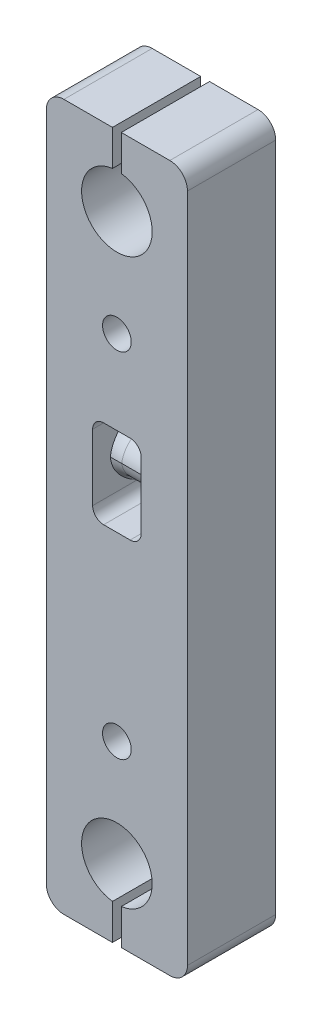
SolidWorks part; units mm, degrees
ref_plane "Front Plane" through (0, 0, 0) normal (0, 0, 1) x (1, 0, 0)
ref_plane "Top Plane" through (0, 0, 0) normal (0, 1, 0) x (1, 0, 0)
ref_plane "Right Plane" through (0, 0, 0) normal (1, 0, 0) x (0, 0, -1)
sketch "Sketch1" plane through (0, 0, 0) normal (0, 0, 1) x (1, 0, 0)
  line L0 (8, 72) -> (8, 8) construction
  line L1 (0, 0) -> (16, 0)
  line L2 (0, 0) -> (0, 80)
  line L3 (0, 80) -> (16, 80)
  line L4 (16, 0) -> (16, 80)
  line L5 (8, 8) -> (8, 0) construction
  line L6 (6.5, 49.25) -> (9.5, 49.25) construction
  line L7 (6.5, 50.5) -> (9.5, 50.5)
  line L8 (6.5, 48) -> (9.5, 48)
  line L9 (6.5, 41.75) -> (9.5, 41.75) construction
  line L10 (6.5, 43) -> (9.5, 43)
  line L11 (6.5, 40.5) -> (9.5, 40.5)
  line L12 (8, 40) -> (16, 40) construction
  circle A0 centre (8, 72) radius 4
  circle A1 centre (8, 8) radius 4
  arc A2 (6.5, 50.5) -> (6.5, 48) centre (6.5, 49.25) ccw
  arc A3 (9.5, 48) -> (9.5, 50.5) centre (9.5, 49.25) ccw
  arc A4 (6.5, 43) -> (6.5, 40.5) centre (6.5, 41.75) ccw
  arc A5 (9.5, 40.5) -> (9.5, 43) centre (9.5, 41.75) ccw
  circle A6 centre (8, 20) radius 1.625
  circle A7 centre (8, 60) radius 1.625
  point P12 (8, 49.25)
  point P17 (8, 41.75)
  dimension "D2" = 8
  dimension "D10" = 3.25
  dimension "D1" = 8
  dimension "D3" = 64
  dimension "D4" = 8
  dimension "D5" = 8
  dimension "D6" = 8
  dimension "D7" = 3
  dimension "D8" = 2.5
  dimension "D9" = 5
  dimension "D11" = 12
  dimension "D12" = 12
extrude "Boss-Extrude1" add sketch "Sketch1" along normal blind 10
fillet "Fillet1" radius 2 4 edges at (0, 0, 5) (16, 0, 5) (16, 80, 5) (0, 80, 5)
sketch "Sketch2" plane through (0, 0, 10) normal (0, 0, 1) x (1, 0, 0)
  line L0 (5.25, 49.25) -> (5.25, 41.75)
  line L1 (10.75, 49.25) -> (10.75, 41.75)
  line L2 (5.25, 49.25) -> (10.75, 49.25)
  line L3 (5.25, 41.75) -> (10.75, 41.75)
  arc A0 (6.5, 50.5) -> (6.5, 48) centre (6.5, 49.25) ccw construction
  arc A1 (6.5, 43) -> (6.5, 40.5) centre (6.5, 41.75) ccw construction
  arc A2 (9.5, 48) -> (9.5, 50.5) centre (9.5, 49.25) ccw construction
  arc A3 (9.5, 40.5) -> (9.5, 43) centre (9.5, 41.75) ccw construction
extrude "Cut-Extrude2" cut sketch "Sketch2" against normal blind 2
fillet "Fillet2" radius 3 6 edges at (5.6161, 42.6339, 8) (10.3839, 42.6339, 8) (10.3839, 48.3661, 8) (5.6161, 48.3661, 8) (8, 43, 8) (8, 48, 8)
sketch "Sketch3" plane through (0, 0, 0) normal (0, 0, -1) x (-1, 0, 0)
  line L0 (-8, 72) -> (-8, 80) construction
  line L1 (-14, 80) -> (-2, 80) construction
  line L2 (-8.5, 72) -> (-8.5, 80)
  line L3 (-7.5, 72) -> (-7.5, 80)
  line L4 (-8, 8) -> (-8, 0) construction
  line L5 (-7.5, 8) -> (-7.5, 0)
  line L6 (-8.5, 8) -> (-8.5, 0)
  arc A1 (-8.5, 72) -> (-7.5, 72) centre (-8, 72) ccw
  arc A2 (-7.5, 80) -> (-8.5, 80) centre (-8, 80) ccw
  circle A3 centre (-8, 72) radius 4 construction
  arc A4 (-7.5, 8) -> (-8.5, 8) centre (-8, 8) ccw
  arc A5 (-8.5, 0) -> (-7.5, 0) centre (-8, 0) ccw
  point P2 (-8, 4)
  point P6 (-8, 76)
  point P19 (0, 0)
  dimension "D1" = 1
extrude "Cut-Extrude3" cut sketch "Sketch3" against normal through all
